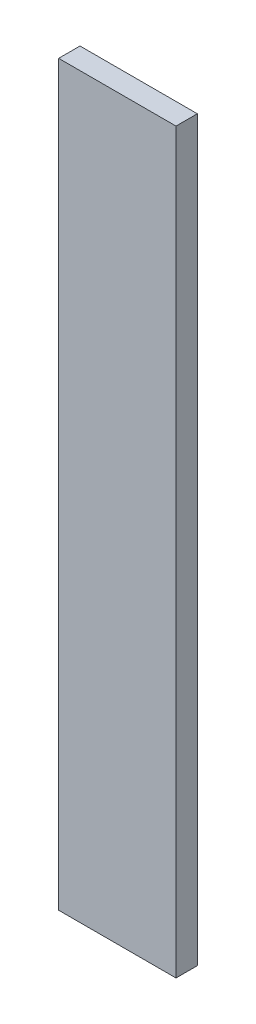
SolidWorks part; units mm, degrees
ref_plane "Front Plane" through (0, 0, 0) normal (0, 0, 1) x (1, 0, 0)
ref_plane "Top Plane" through (0, 0, 0) normal (0, 1, 0) x (1, 0, 0)
ref_plane "Right Plane" through (0, 0, 0) normal (1, 0, 0) x (0, 0, -1)
sketch "Sketch1" plane through (0, 0, 0) normal (0, 0, 1) x (1, 0, 0)
  line L0 (23, 395) -> (23, 0) construction
  line L1 (-23, 0) -> (43, 0)
  line L2 (-23, 0) -> (-23, 415)
  line L3 (-23, 415) -> (43, 415)
  line L4 (43, 0) -> (43, 415)
  line L5 (-23, 395) -> (23, 395) construction
  line L7 (23, 395) -> (-23, 395)
  line L8 (23, 395) -> (23, 0)
  line L9 (23, 0) -> (-23, 0)
  line L10 (-23, 395) -> (-23, 0)
  point P9 (0, 395)
  dimension "D1" = 20
  dimension "D2" = 20
extrude "Boss-Extrude1" add sketch "Sketch1" against normal blind 6 contours L7 L8 L1 L4 L3 L2 region at (29.7072, 227.2072, 0)
sketch "Sketch2" plane through (0, 0, 0) normal (0, 0, 1) x (1, 0, 0)
  line L1 (43, 415) -> (-23, 415)
  line L2 (43, 415) -> (43, 0)
  line L3 (43, 0) -> (-23, 0)
  line L4 (-23, 415) -> (-23, 0)
extrude "Boss-Extrude2" add sketch "Sketch2" along normal blind 6
